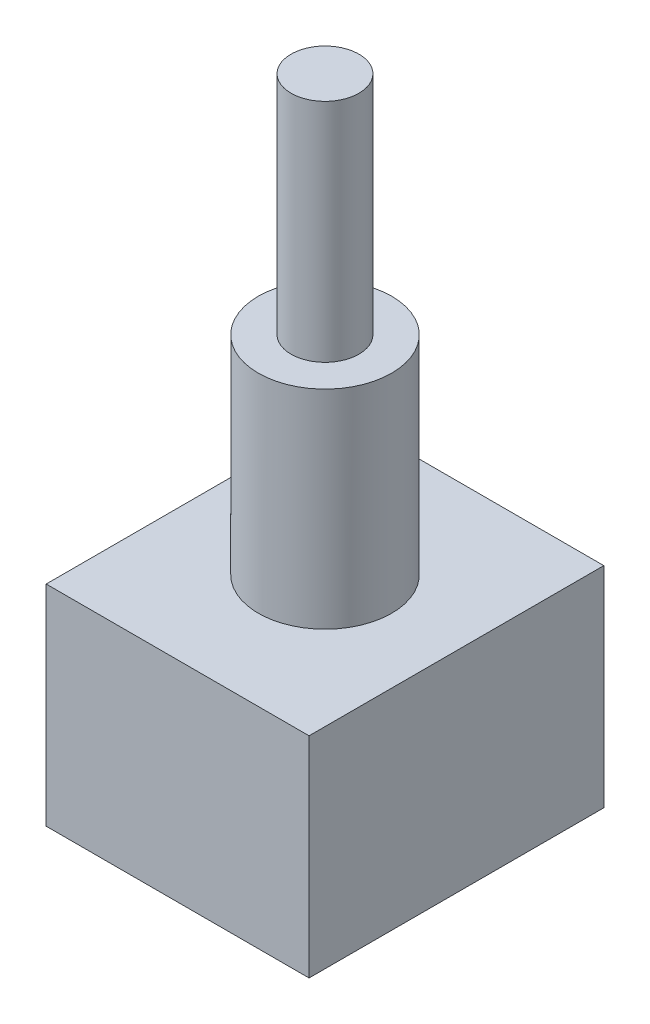
SolidWorks part; units mm, degrees
ref_plane "Front Plane" through (0, 0, 0) normal (0, 0, 1) x (1, 0, 0)
ref_plane "Top Plane" through (0, 0, 0) normal (0, 1, 0) x (1, 0, 0)
ref_plane "Right Plane" through (0, 0, 0) normal (1, 0, 0) x (0, 0, -1)
sketch "Sketch1" plane through (0, 0, 0) normal (0, 1, 0) x (1, 0, 0)
  line L1 (-5.815, -6.52) -> (5.815, -6.52)
  line L2 (-5.815, -6.52) -> (-5.815, 6.52)
  line L3 (-5.815, 6.52) -> (5.815, 6.52)
  line L4 (5.815, -6.52) -> (5.815, 6.52)
  line L5 (-5.815, -6.52) -> (5.815, 6.52) construction
  line L6 (-5.815, 6.52) -> (5.815, -6.52) construction
  point P0 (0, 0)
  dimension "D1" = 11.63
  dimension "D2" = 13.04
extrude "Boss-Extrude1" add sketch "Sketch1" along normal blind 9.28
sketch "Sketch3" plane through (0, 9.28, 0) normal (0, 1, 0) x (1, 0, 0)
  circle A0 centre (0, 0) radius 2.95
  dimension "D1" = 5.9
extrude "Boss-Extrude3" add sketch "Sketch3" along normal blind 9.2
sketch "Sketch4" plane through (0, 18.48, 0) normal (0, 1, 0) x (1, 0, 0)
  circle A0 centre (0, 0) radius 1.5
  dimension "D1" = 3
extrude "Boss-Extrude4" add sketch "Sketch4" along normal blind 10
